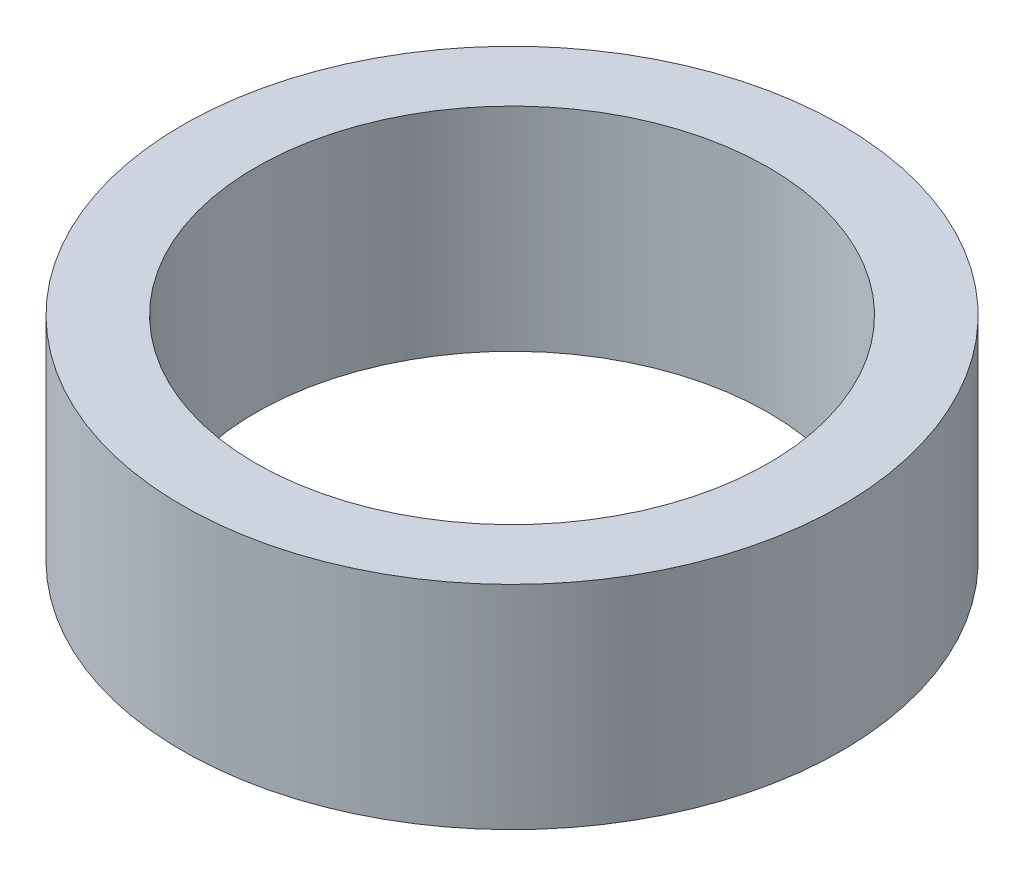
SolidWorks part; units mm, degrees
ref_plane "Front Plane" through (0, 0, 0) normal (0, 0, 1) x (1, 0, 0)
ref_plane "Top Plane" through (0, 0, 0) normal (0, 1, 0) x (1, 0, 0)
ref_plane "Right Plane" through (0, 0, 0) normal (1, 0, 0) x (0, 0, -1)
sketch "Sketch1" plane through (0, 0, 0) normal (0, 1, 0) x (1, 0, 0)
  circle A0 centre (0, 0) radius 45
  dimension "FLANGE_OD" = 90
extrude "Boss-Extrude1" add sketch "Sketch1" along normal blind 29
sketch "Sketch2" plane through (0, 0, 0) normal (0, 1, 0) x (1, 0, 0)
  circle A0 centre (0, 0) radius 35
  dimension "BORE_D" = 70
extrude "Cut-Extrude1" cut sketch "Sketch2" along normal through all
sketch "Sketch3" plane through (0, 29, 0) normal (0, 1, 0) x (1, 0, 0)
  circle A0 centre (0, 0) radius 20.2615 construction
  circle A1 centre (-20.2615, 0) radius 1.5634
  dimension "BOLT_D" = 3.1267
  dimension "BOLT_PCD" = 40.523
extrude "Cut-Extrude2" cut sketch "Sketch3" against normal blind 26.0788 rebuild error yes
pattern_circular "CirPattern1" count 4 over 360 rebuild error yes
